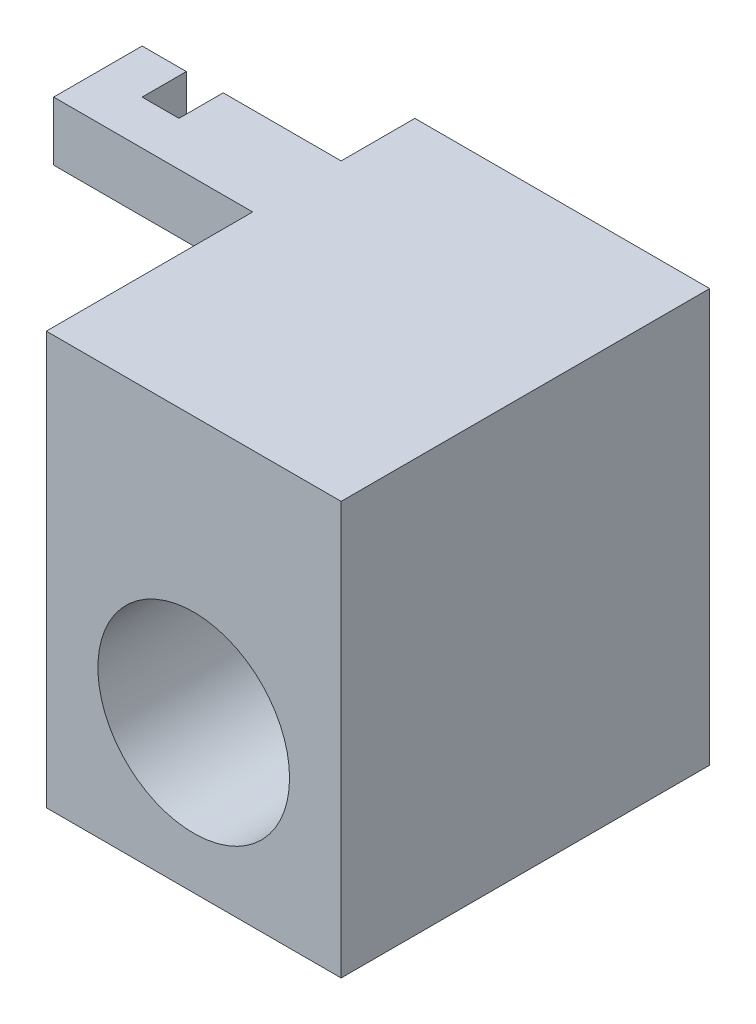
SolidWorks part; units mm, degrees
ref_plane "Front Plane" through (0, 0, 0) normal (0, 0, 1) x (1, 0, 0)
ref_plane "Top Plane" through (0, 0, 0) normal (0, 1, 0) x (1, 0, 0)
ref_plane "Right Plane" through (0, 0, 0) normal (1, 0, 0) x (0, 0, -1)
sketch "Sketch1" plane through (0, 0, 0) normal (0, 0, 1) x (1, 0, 0)
  line L1 (0, 0) -> (-20, 0)
  line L2 (0, 0) -> (0, -28)
  line L3 (0, -28) -> (-20, -28)
  line L4 (-20, 0) -> (-20, -28)
  dimension "D1" = 20
  dimension "D2" = 28
extrude "Boss-Extrude1" add sketch "Sketch1" along normal blind 25
sketch "Sketch2" plane through (0, 0, 25) normal (0, 0, 1) x (1, 0, 0)
  line L0 (-20, 0) -> (-20, -28) construction
  line L1 (0, 0) -> (-20, 0) construction
  circle A0 centre (-10, -18) radius 6.5
  point P4 (-20, -14)
  point P7 (-10, 0)
  dimension "D1" = 4
  dimension "D2" = 0
  dimension "D3" = 13
extrude "Cut-Extrude1" cut sketch "Sketch2" against normal blind 40
sketch "Sketch3" plane through (-20, 0, 0) normal (-1, 0, 0) x (0, 0, 1)
  line L1 (0, 0) -> (0, -28) construction
  circle A0 centre (8, -18) radius 2.75
  point P7 (0, -14)
  dimension "D1" = 8
  dimension "D2" = 4
  dimension "D3" = 5.5
extrude "Cut-Extrude2" cut sketch "Sketch3" against normal blind 10
thread "Thread1" pitch 2.1167 method cut profile "Thread Profile1" start angle 0, offset 0, length 10, pitch 2.1167, diameter 5.5
ref_plane "Plane1" through (-20, -18, 5.25) normal (0, -1, 0) x (0, 0, -1)
sketch "Thread Profile1" plane through (-20, -18, 5.25) normal (0, -1, 0) x (0, 0, -1)
  line L0 (0, 0) -> (0, 2.1167) construction
  line L1 (0, 0) -> (1.1457, 0.6615)
  line L2 (1.1457, 0.6615) -> (1.1457, 0.926)
  line L3 (1.1457, 0.926) -> (0, 1.5875)
  line L4 (1.1457, 0.7937) -> (0, 0.7937) construction
  line L11 (0, 0) -> (0, 1.5875)
  point P2 (0, 0)
  dimension "Pitch" = 2.1167
  dimension "Profile_Angle" = 60
  dimension "Profile_Land" = 0.2646
  dimension "Profile_Height" = 1.1457
sketch "Sketch6" plane through (-20, 0, 0) normal (-1, 0, 0) x (0, 0, 1)
  circle A0 centre (8, -18) radius 3.75
  dimension "D1" = 7.5
extrude "Cut-Extrude3" cut sketch "Sketch6" against normal blind 1
sketch "Sketch7" plane through (-20, 0, 0) normal (-1, 0, 0) x (0, 0, 1)
  line L0 (25, 0) -> (0, 0) construction
  line L1 (5, -4) -> (11, -4)
  line L2 (5, -4) -> (5, 0)
  line L3 (5, 0) -> (11, 0)
  line L4 (11, -4) -> (11, 0)
  line L5 (0, 0) -> (0, -28) construction
  dimension "D1" = 0
  dimension "D2" = 5
  dimension "D3" = 4
  dimension "D4" = 6
extrude "Boss-Extrude2" add sketch "Sketch7" along normal blind 13.5
sketch "Sketch8" plane through (0, -4, 0) normal (0, -1, 0) x (-1, 0, 0)
  line L0 (33.5, -5) -> (20, -5) construction
  line L1 (30.5, -5) -> (28, -5)
  line L2 (30.5, -5) -> (30.5, -8)
  line L3 (30.5, -8) -> (28, -8)
  line L4 (28, -5) -> (28, -8)
  line L5 (33.5, -5) -> (33.5, -11) construction
  point P8 (33.5, -8)
  dimension "D1" = 0
  dimension "D2" = 3
  dimension "D3" = 2.5
extrude "Cut-Extrude4" cut sketch "Sketch8" against normal blind 10
